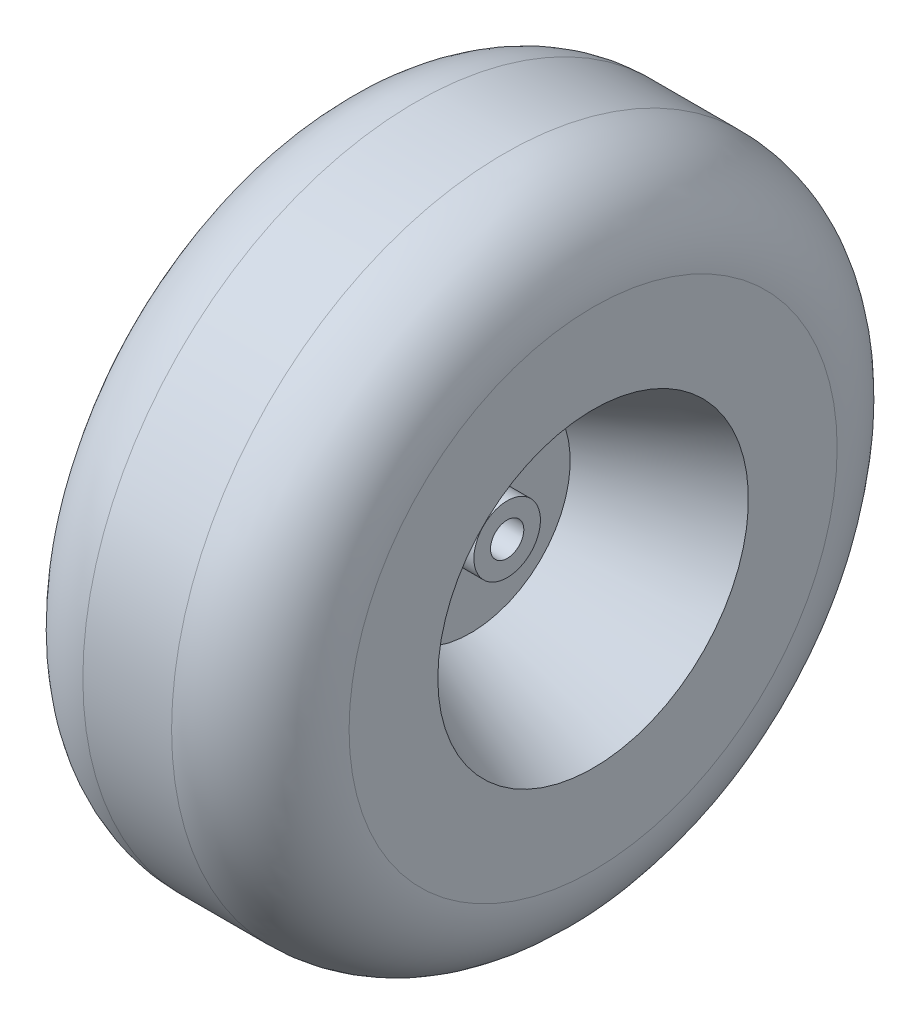
SolidWorks part; units mm, degrees
ref_plane "Front Plane" through (0, 0, 0) normal (0, 0, 1) x (1, 0, 0)
ref_plane "Top Plane" through (0, 0, 0) normal (0, 1, 0) x (1, 0, 0)
ref_plane "Right Plane" through (0, 0, 0) normal (1, 0, 0) x (0, 0, -1)
sketch "Sketch1" plane through (0, 0, 0) normal (0, 0, 1) x (1, 0, 0)
  line L0 (0, 0) -> (0, 190.5) construction
  line L1 (-76.2, 190.5) -> (76.2, 190.5) construction
  line L2 (76.2, 190.5) -> (76.2, 88.9) construction
  line L3 (-76.2, 0) -> (76.2, 0) construction
  line L4 (0, 0) -> (0, 9.525) construction
  line L5 (-26.9875, 9.525) -> (26.9875, 9.525)
  line L6 (76.2, 88.9) -> (76.2, 0) construction
  line L7 (26.9875, 9.525) -> (26.9875, 19.05)
  line L8 (26.9875, 19.05) -> (6.1126, 19.05)
  line L9 (6.1126, 19.05) -> (6.1126, 56.9746)
  line L10 (6.1126, 56.9746) -> (76.2, 88.9)
  line L11 (-25.4, 190.5) -> (25.4, 190.5)
  line L12 (76.2, 88.9) -> (76.2, 139.7)
  line L13 (-76.2, 88.9) -> (-76.2, 0) construction
  line L14 (-76.2, 190.5) -> (-76.2, 88.9) construction
  line L15 (-76.2, 88.9) -> (-76.2, 139.7)
  line L16 (-6.1126, 56.9746) -> (-76.2, 88.9)
  line L17 (-6.1126, 19.05) -> (-6.1126, 56.9746)
  line L18 (-26.9875, 19.05) -> (-6.1126, 19.05)
  line L19 (-26.9875, 9.525) -> (-26.9875, 19.05)
  line L20 (25.4, 190.5) -> (25.4, 139.7) construction
  line L21 (25.4, 139.7) -> (76.2, 139.7) construction
  arc A0 (25.4, 190.5) -> (76.2, 139.7) centre (25.4, 139.7) cw
  arc A1 (-25.4, 190.5) -> (-76.2, 139.7) centre (-25.4, 139.7) ccw
  point P11 (0, 9.525)
  point P14 (0, 0)
  dimension "D8" = 50.8
  dimension "D1" = 190.5
  dimension "D2" = 76.2
  dimension "D3" = 101.6
  dimension "D4" = 9.525
  dimension "D5" = 49.2125
  dimension "D6" = 9.525
revolve "Revolve1" add sketch "Sketch1" angle 360 about L3
sketch "Sketch2" plane through (0, 0, 0) normal (1, 0, 0) x (0, 0, -1)
  line L0 (0, 0) -> (0, -190.5) construction
  line L1 (0, 0) -> (0, 190.5)
  circle A0 centre (0, 0) radius 190.5
